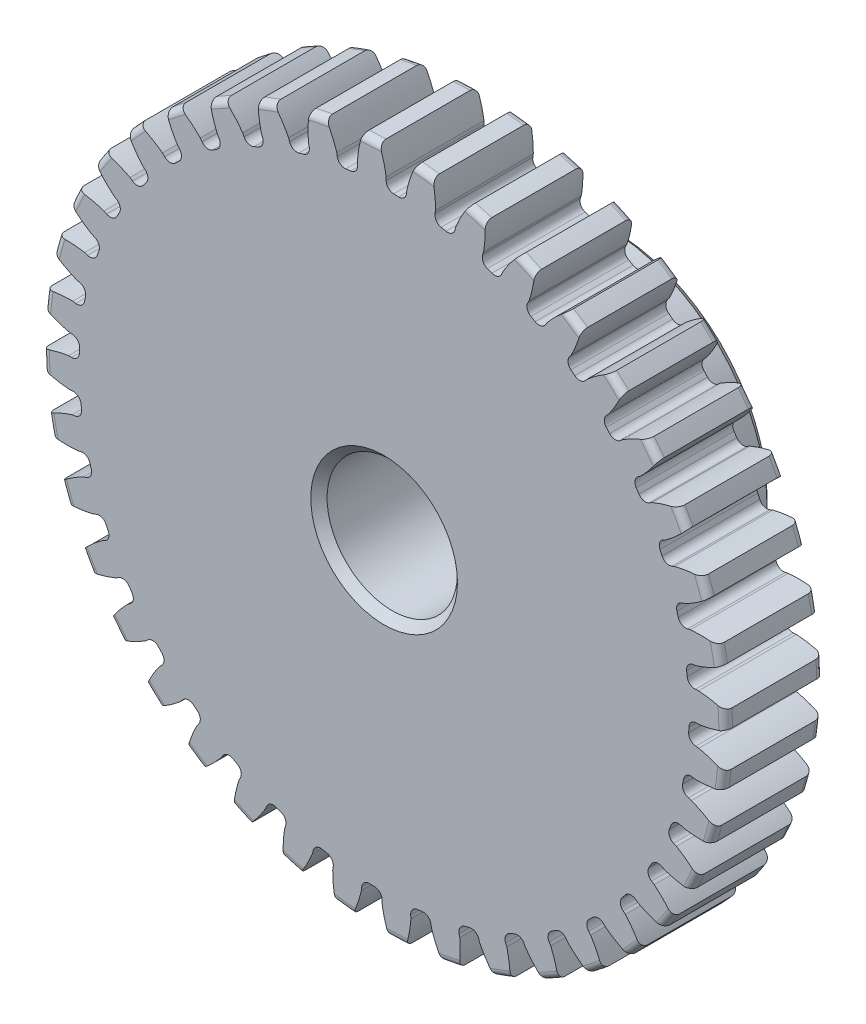
SolidWorks part; units mm, degrees
ref_plane "Front" through (0, 0, 0) normal (0, 0, 1) x (1, 0, 0)
ref_plane "Top" through (0, 0, 0) normal (0, 1, 0) x (1, 0, 0)
ref_plane "Right" through (0, 0, 0) normal (1, 0, 0) x (0, 0, -1)
sketch "Sketch1" plane through (0, 0, 0) normal (0, 0, 1) x (1, 0, 0)
  line L0 (-508, 0) -> (508, 0) construction
  circle A0 centre (0, 0) radius 16.637
  circle A1 centre (0, 0) radius 15.875 construction
  circle A3 centre (0, 0) radius 14.8511 construction
  dimension "D3" = 0.762
  dimension "D1" = 1.7859
extrude "Boss-Extrude1" add sketch "Sketch1" against normal blind 4.7625
sketch "Sketch2" plane through (0, 0, 0) normal (1, 0, 0) x (0, 0, -1)
  line L0 (4.7625, 0) -> (11.1125, 0)
  line L1 (4.7625, 0) -> (4.7625, 7.9375)
  line L2 (4.7625, 7.9375) -> (11.1125, 7.9375)
  line L3 (11.1125, 7.9375) -> (11.1125, 0)
  point P5 (11.1125, -7.9375)
  point P6 (0, -16.637)
  point P7 (4.7625, -16.637)
  point P9 (0, 16.637)
revolve "Revolve1" add sketch "Sketch2" angle 360 mid plane about L0
fillet "Fillet2" radius 0.3327 3 edges at (16.637, 0, -4.7625) (16.637, 0, 0) (7.9375, 0, -4.7625)
sketch "Sketch3" plane through (0, 0, 0) normal (0, 0, 1) x (1, 0, 0)
  line L0 (0, 0) -> (0, 16.637) construction
  line L1 (-3.8482, 14.8798) -> (0, 15.875)
  line L2 (-9.5921, 15.875) -> (9.5921, 15.875) construction
  line L3 (-9.2865, 13.4733) -> (9.2865, 18.2767) construction
  line L4 (-3.8482, 14.8798) -> (0, 0) construction
  line L5 (-9.8154, 11.8269) -> (0, 0) construction
  line L6 (-9.8154, 11.8269) -> (-1.5766, 18.6644) construction
  line L7 (-2.6833, 15.1333) -> (0, 0) construction
  line L8 (-2.6833, 15.1333) -> (0.0563, 15.6191) construction
  arc A0 (-3.8482, 14.8798) -> (-9.8154, 11.8269) centre (0, 0) ccw
  circle A1 centre (0, 0) radius 15.875 construction
  circle A2 centre (0, 0) radius 15.3693 construction
  arc A3 (-3.8482, 14.8798) -> (-2.6833, 15.1333) centre (0, 0) cw
  circle A4 centre (0, 0) radius 16.637 construction
  point P6 (0, 15.875)
  dimension "D1" = 3.9748
  dimension "D3" = 10.7065
  dimension "D5" = 2.7823
  dimension "D2" = 6.7571
  dimension "D4" = 1.1924
sketch "Sketch4" plane through (0, 0, 0) normal (0, 0, 1) x (1, 0, 0)
  line L0 (0, 0) -> (0.6228, 15.8505) construction
  line L1 (0.0999, 15.369) -> (0.0999, 14.8507)
  line L2 (0, 15.875) -> (1.2455, 15.8261) construction
  line L3 (1.1063, 15.3295) -> (1.0656, 14.8128)
  line L4 (0.0999, 14.8507) -> (0, 0) construction
  line L5 (0, 0) -> (0, 16.637) construction
  line L6 (-9.8154, 11.8269) -> (-1.5766, 18.6644) construction
  line L7 (-9.8154, 11.8269) -> (-1.5766, 18.6644) construction
  arc A0 (1.0656, 14.8128) -> (0.0999, 14.8507) centre (0, 0) ccw
  arc A1 (0, 15.875) -> (1.2455, 15.8261) centre (0, 0) cw construction
  circle A2 centre (0, 0) radius 15.875 construction
  circle A3 centre (0, 0) radius 15.3693 construction
  circle A4 centre (0, 0) radius 14.8511 construction
  arc A5 (3.0362, 18.4832) -> (-1.5766, 18.6644) centre (0, 0) ccw
  spline S0 degree 2 poles (-1.5766, 18.6644) (-0.1802, 17.2094) (0.0999, 15.369) knots 0 0 0 1 1 1
  spline S1 degree 2 poles (3.0362, 18.4832) (1.5298, 17.1422) (1.1063, 15.3295) knots 0 0 0 1 1 1
  dimension "D1" = 1.2468
extrude "Cut-Extrude1" cut sketch "Sketch4" against normal through all
fillet "Fillet1" radius 0.374 2 edges at (1.0656, 14.8128, -2.3813) (0.0999, 14.8507, -2.3813)
pattern_circular "CirPattern1" count 40 over 360 about axis through (0, 0, -4.7625) along (0, 0, 1) of "Cut-Extrude1", "Fillet1"
sketch "Sketch5" plane through (0, 0, 0) normal (0, 0, 1) x (1, 0, 0)
  circle A0 centre (0, 0) radius 3.175
  circle A1 centre (0, 0) radius 1.5875 construction
  dimension "Bore Min" = 6.35
  dimension "Bore Max" = 3.175
extrude "Cut-Extrude2" cut sketch "Sketch5" against normal through all
chamfer "Chamfer1" distance 0.3969 angle 45 3 edges at (7.9375, 0, -11.1125) (3.175, 0, 0) (3.175, 0, -11.1125)
sketch "Pitch Dia" plane through (0, 0, 0) normal (0, 0, 1) x (1, 0, 0)
  circle A0 centre (0, 0) radius 15.875 construction
  circle A1 centre (0, 0) radius 15.875 construction
equation "\"D1@Boss-Extrude1\" = \"Face Wd@Sketch2\""
equation "\"D2@Sketch3\" = \"D1@Sketch3\"*1.7"
equation "\"D3@Sketch3\" = \"D1@Sketch3\"+\"D2@Sketch3\"-.001"
equation "\"D4@Sketch3\" = \"D1@Sketch3\"*.3"
equation "\"D5@Sketch3\" = \"D1@Sketch3\"-\"D4@Sketch3\""
equation "\"D1@Sketch4\" = 1.5708/(\"Number of Teeth@Sketch1\"/\"Ptich Dia@Sketch1\")"
equation "\"D1@Chamfer1\" = \"B Hub Dia@Sketch2\"*.025"
equation "\"D1@CirPattern1\" = \"Number of Teeth@Sketch1\""
equation "\"D1@Fillet1\" = \"D1@Sketch4\"*.3"
equation "\"D1@Fillet2\" = \"OD@Sketch1\"*.01"
equation "\"D1@Sketch1\" = 2.250/(\"Number of Teeth@Sketch1\"/\"Ptich Dia@Sketch1\")"
